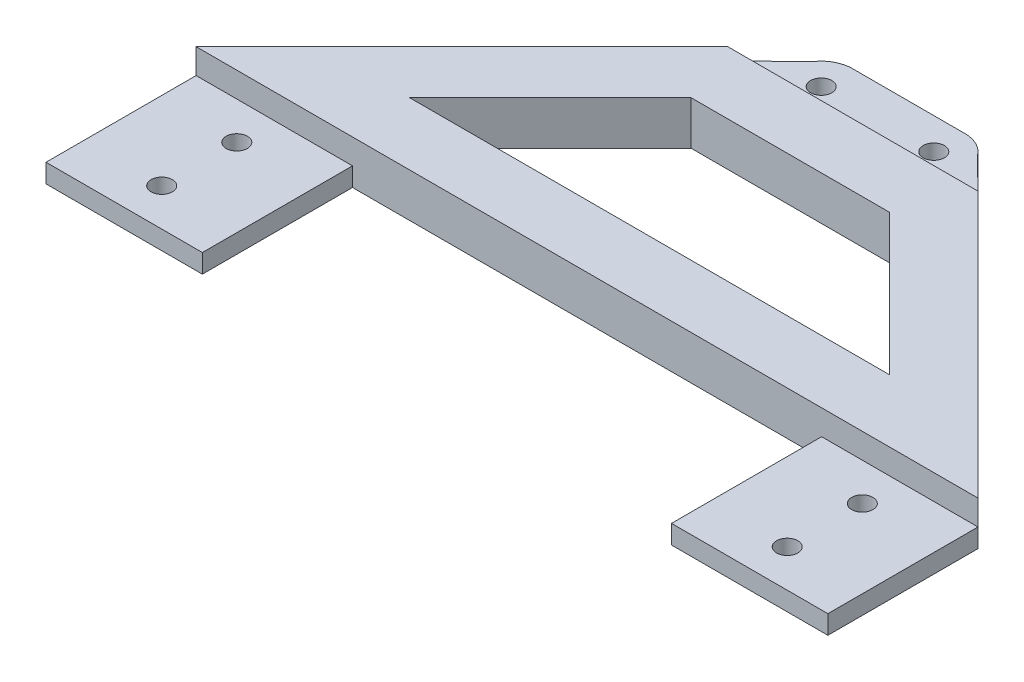
SolidWorks part; units mm, degrees
ref_plane "Front Plane" through (0, 0, 0) normal (0, 0, 1) x (1, 0, 0)
ref_plane "Top Plane" through (0, 0, 0) normal (0, 1, 0) x (1, 0, 0)
ref_plane "Right Plane" through (0, 0, 0) normal (1, 0, 0) x (0, 0, -1)
sketch "Triangle" plane through (0, 0, 0) normal (0, 1, 0) x (1, 0, 0)
  line L0 (0, 0) -> (125, 0)
  line L1 (125, 0) -> (82.5, 42.5)
  line L2 (42.5, 42.5) -> (0, 0)
  line L3 (62.5, 0) -> (62.5, 42.5) construction
  line L4 (82.5, 42.5) -> (42.5, 42.5)
  line L5 (24.1421, 10) -> (100.8579, 10)
  line L6 (100.8579, 10) -> (78.3579, 32.5)
  line L7 (78.3579, 32.5) -> (46.6421, 32.5)
  line L8 (46.6421, 32.5) -> (24.1421, 10)
  dimension "D1" = 125
  dimension "D2" = 40
  dimension "D3" = 45
  dimension "D4" = 45
  dimension "D5" = 10
  dimension "D6" = 10
  dimension "D7" = 10
  dimension "D8" = 45
  dimension "D9" = 10
  dimension "D10" = 45
sketch "Bearing Mounts" plane through (0, 0, 0) normal (0, 1, 0) x (1, 0, 0)
  line L0 (12.5, -24) -> (12.5, 0) construction
  line L1 (25, 0) -> (0, 0)
  line L2 (25, 0) -> (25, -24)
  line L3 (25, -24) -> (0, -24)
  line L4 (0, 0) -> (0, -24)
  line L5 (112.5, -24) -> (112.5, 0) construction
  line L6 (125, 0) -> (100, 0)
  line L7 (125, 0) -> (125, -24)
  line L8 (125, -24) -> (100, -24)
  line L9 (100, 0) -> (100, -24)
  line L10 (100, -24) -> (25, -24) construction
  line L11 (62.5, -24) -> (62.5, 68.4083) construction
  line L14 (62.5, 42.5) -> (62.5, -51.9511) construction
  dimension "D1" = 24
  dimension "D2" = 25
  dimension "D3" = 24
  dimension "D4" = 25
  dimension "D5" = 100
extrude "Bearing Mount Plates" add sketch "Bearing Mounts" along normal blind 3
extrude "Bridge" add sketch "Triangle" along normal blind 7
sketch "M3 Bearing Holes" plane through (0, 0, 0) normal (0, -1, 0) x (1, 0, 0)
  line L0 (125, 24) -> (125, 0) construction
  line L2 (125, 0) -> (82.5, -42.5) construction
  line L4 (100, 0) -> (100, 24) construction
  line L5 (0, 24) -> (25, 24) construction
  line L6 (0, 0) -> (125, 0) construction
  line L7 (25, 24) -> (25, 0) construction
  line L12 (100, 24) -> (125, 24) construction
  circle A0 centre (112.5, 6) radius 1.7
  circle A1 centre (112.5, 18) radius 1.7
  circle A2 centre (12.5, 6) radius 1.7
  circle A3 centre (12.5, 18) radius 1.7
  dimension "D1" = 3.4
  dimension "D5" = 6
  dimension "D10" = 3.4
  dimension "D2" = 6
  dimension "D3" = 12.5
  dimension "D4" = 6
  dimension "D6" = 12.5
  dimension "D7" = 12.5
  dimension "D8" = 6
  dimension "D9" = 12.5
extrude "Bearing Mount Holes" cut sketch "M3 Bearing Holes" against normal up to surface (3 mm away) up to face at (12.5, 3, 12)
sketch "Belt Mount" plane through (0, 0, 0) normal (0, -1, 0) x (1, 0, 0)
  line L1 (53.5, -41.4289) -> (71.5, -41.4289)
  line L2 (42.5, -42.5) -> (0, 0) construction
  line L3 (53.5, -51.4289) -> (71.5, -51.4289)
  line L4 (125, 0) -> (82.5, -42.5) construction
  arc A0 (53.5, -41.4289) -> (53.5, -51.4289) centre (53.5, -46.4289) ccw
  arc A1 (71.5, -51.4289) -> (71.5, -41.4289) centre (71.5, -46.4289) ccw
  dimension "D2" = 5
  dimension "D1" = 18
extrude "Belt Mount Plate" add sketch "Belt Mount" against normal blind 5
sketch "M3 Belt Holes" plane through (0, 0, 0) normal (0, -1, 0) x (1, 0, 0)
  circle A0 centre (53.5, -46.4289) radius 1.7
  circle A1 centre (71.5, -46.4289) radius 1.7
  dimension "D1" = 3.4
extrude "Belt Mount Screw Holes" cut sketch "M3 Belt Holes" against normal up to surface (5 mm away) up to face at (62.5, 5, -47.5149)
sketch "Sketch6" plane through (0, 0, 0) normal (0, -1, 0) x (1, 0, 0)
  line L0 (42.5, -42.5) -> (49.5, -49.4289)
  line L1 (49.5, -49.4289) -> (50.4075, -42.5)
  line L2 (50.4075, -42.5) -> (42.5, -42.5)
  line L3 (82.5, -42.5) -> (75.5, -49.4289)
  line L4 (75.5, -49.4289) -> (74.5925, -42.5)
  line L5 (74.5925, -42.5) -> (82.5, -42.5)
  line L6 (53.5, -49.4289) -> (94.0576, -49.4289) construction
  line L7 (94.0576, -49.4289) -> (23.5138, -49.4289) construction
  line L9 (53.5, -51.4289) -> (71.5, -51.4289) construction
  arc A0 (53.5, -41.4289) -> (53.5, -51.4289) centre (53.5, -46.4289) ccw construction
  arc A3 (71.5, -51.4289) -> (71.5, -41.4289) centre (71.5, -46.4289) ccw construction
  dimension "D1" = 2
extrude "Boss-Extrude1" add sketch "Sketch6" against normal up to surface (5 mm away) up to face at (71.5, 5, -48.1289)
